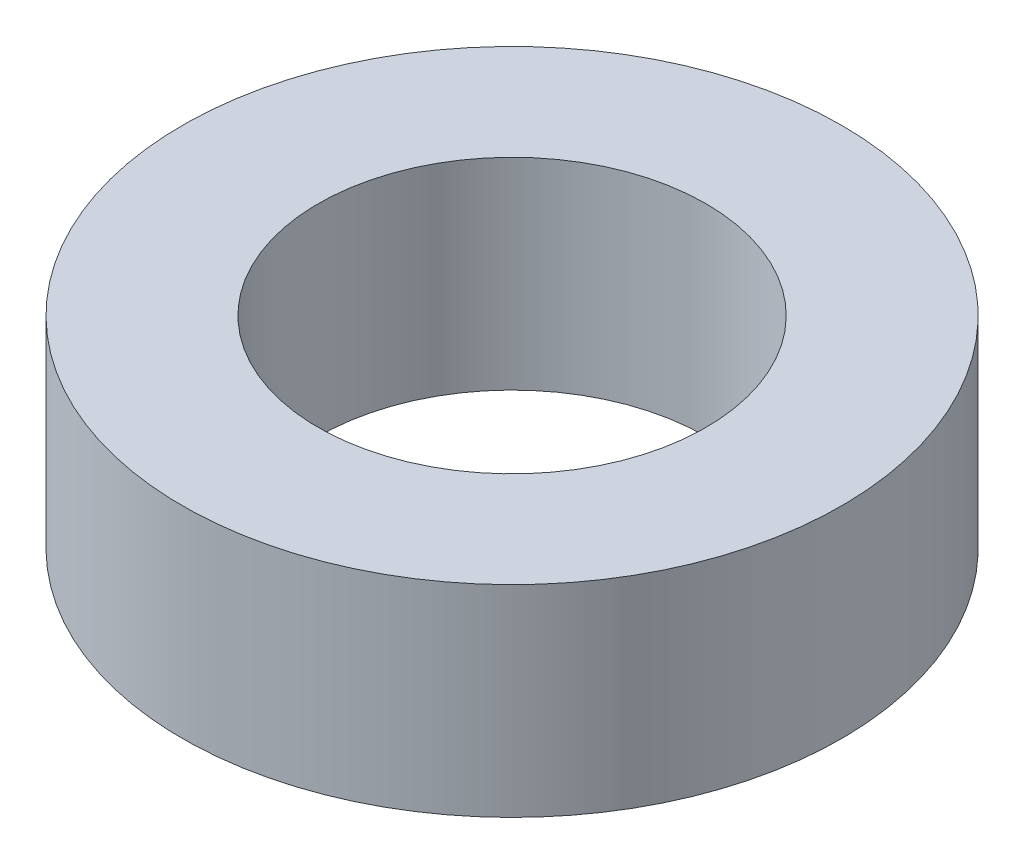
SolidWorks part; units mm, degrees
ref_plane "Front Plane" through (0, 0, 0) normal (0, 0, 1) x (1, 0, 0)
ref_plane "Top Plane" through (0, 0, 0) normal (0, 1, 0) x (1, 0, 0)
ref_plane "Right Plane" through (0, 0, 0) normal (1, 0, 0) x (0, 0, -1)
sketch "Sketch1" plane through (0, 0, 0) normal (0, 1, 0) x (1, 0, 0)
  circle A0 centre (0, 0) radius 42.5
  dimension "FLANGE_OD" = 85
extrude "Boss-Extrude1" add sketch "Sketch1" along normal blind 26
sketch "Sketch2" plane through (0, 0, 0) normal (0, 1, 0) x (1, 0, 0)
  circle A0 centre (0, 0) radius 25
  dimension "BORE_D" = 50
extrude "Cut-Extrude1" cut sketch "Sketch2" along normal through all
sketch "Sketch3" plane through (0, 26, 0) normal (0, 1, 0) x (1, 0, 0)
  circle A0 centre (0, 0) radius 15.3181 construction
  circle A1 centre (-15.3181, 0) radius 3.1203
  dimension "BOLT_D" = 6.2407
  dimension "BOLT_PCD" = 30.6361
extrude "Cut-Extrude2" cut sketch "Sketch3" against normal blind 25.1132 rebuild error yes
pattern_circular "CirPattern1" count 8 over 360 rebuild error yes
